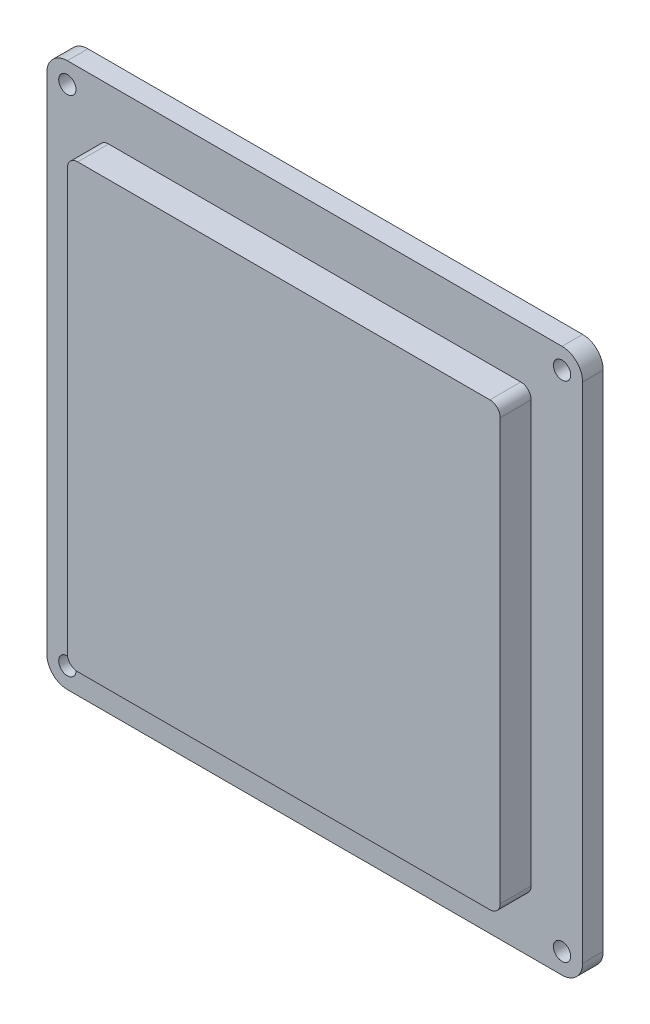
SolidWorks part; units mm, degrees
ref_plane "前视基准面" through (0, 0, 0) normal (0, 0, 1) x (1, 0, 0)
ref_plane "上视基准面" through (0, 0, 0) normal (0, 1, 0) x (1, 0, 0)
ref_plane "右视基准面" through (0, 0, 0) normal (1, 0, 0) x (0, 0, -1)
sketch "草图1" plane through (0, 0, 0) normal (0, 0, 1) x (1, 0, 0)
  line L5 (-130, -132.125) -> (130, -132.125)
  line L6 (-130, -132.125) -> (-130, 132.125)
  line L7 (-130, 132.125) -> (130, 132.125)
  line L8 (130, -132.125) -> (130, 132.125)
  line L9 (-130, -132.125) -> (130, 132.125) construction
  line L10 (-130, 132.125) -> (130, -132.125) construction
  point P0 (0, 0)
  dimension "D1" = 260
  dimension "D2" = 264.25
extrude "凸台-拉伸1" add sketch "草图1" along normal blind 10
fillet "圆角1" radius 10 4 edges at (130, -132.125, 5) (-130, -132.125, 5) (-130, 132.125, 5) (130, 132.125, 5)
hole_wizard "Ø8.4 (8.4) 直径孔1" positions "草图2" profile "草图3" hole size "Ø8.4" standard "GB" end condition through all
sketch "草图2" plane through (0, 0, 0) normal (0, 0, 1) x (1, 0, 0)
  point P0 (-120, 122.125)
  point P3 (120, 122.125)
  point P6 (120, -122.125)
  point P9 (-120, -122.125)
sketch "草图3" plane through (-120, 122.125, 0) normal (1, 0, 0) x (0, 1, 0)
  line L0 (0, 0) -> (0, 10)
  line L1 (0, 10) -> (4.2, 10)
  line L2 (4.2, 10) -> (4.2, 0)
  line L5 (4.2, 0) -> (0, 0)
  line L11 (0, -6.35) -> (0, 107.95) construction
  dimension "通孔孔直径" = 8.4
  dimension "通孔孔深度" = 10
sketch "草图4" plane through (0, 0, 10) normal (0, 0, 1) x (1, 0, 0)
  line L1 (105, -107.125) -> (-105, -107.125)
  line L2 (105, -107.125) -> (105, 107.125)
  line L3 (105, 107.125) -> (-105, 107.125)
  line L4 (-105, -107.125) -> (-105, 107.125)
  line L5 (105, -107.125) -> (-105, 107.125) construction
  line L6 (105, 107.125) -> (-105, -107.125) construction
  point P0 (0, 0)
  dimension "D1" = 214.25
  dimension "D2" = 210
extrude "凸台-拉伸2" add sketch "草图4" along normal blind 15
fillet "圆角2" radius 5 4 edges at (-105, -107.125, 17.5) (-105, 107.125, 17.5) (105, 107.125, 17.5) (105, -107.125, 17.5)
